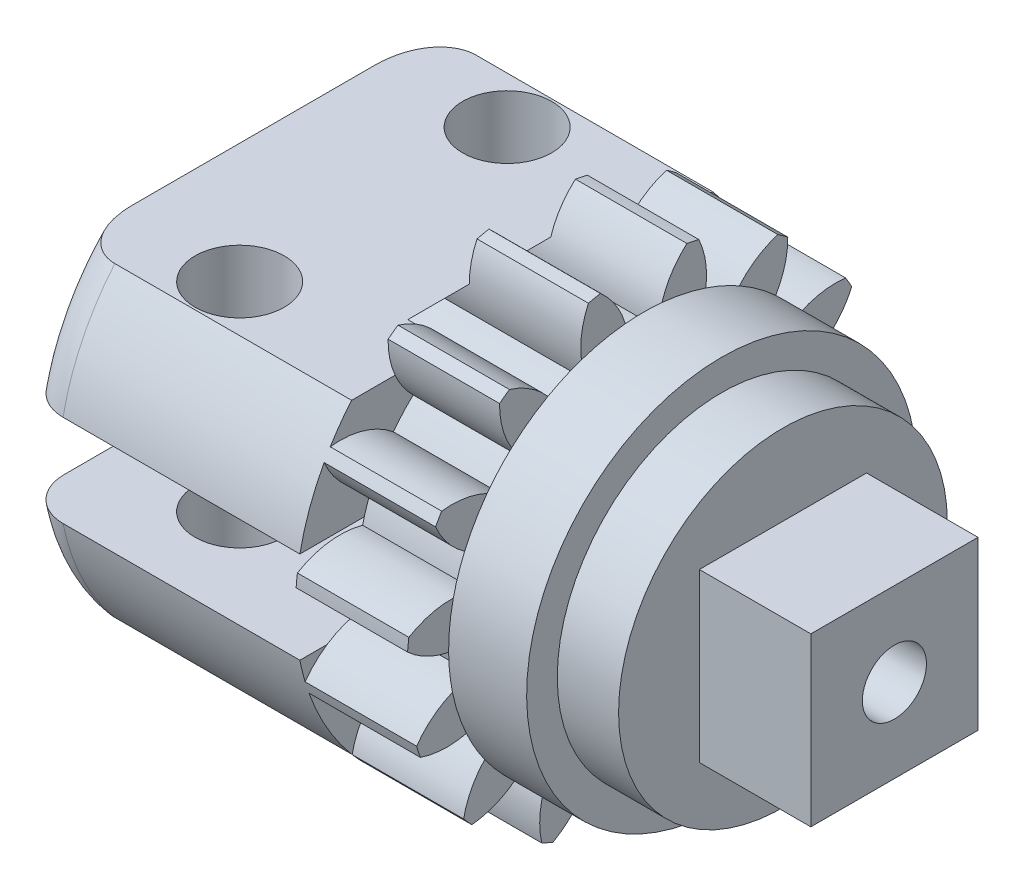
SolidWorks part; units mm, degrees
material "PET"
ref_plane "Plane1" through (0, 0, 0) normal (0, 0, 1) x (1, 0, 0)
ref_plane "Plane2" through (0, 0, 0) normal (0, 1, 0) x (1, 0, 0)
ref_plane "Plane3" through (0, 0, 0) normal (1, 0, 0) x (0, 0, -1)
sketch "HoldingSke" plane through (0, 0, 0) normal (0, 1, 0) x (1, 0, 0)
  line L0 (0, 0) -> (0.9659, -0.2588)
  line L1 (-15, 0) -> (100, 0) construction
  line L2 (0, 0) -> (-2.1039, 2.3779)
  line L3 (0, 0) -> (-11.863, 4.5341)
  line L4 (0, 0) -> (8.3417, 2.2352)
  line L5 (0, 0) -> (-46.8476, -17.4728)
  line L6 (0, 0) -> (-3.3159, -2.2372)
  line L7 (-2.1039, 2.3779) -> (8.6586, 51.2059)
  line L8 (-76.2, 54.61) -> (-76.1, 54.61)
  line L9 (-71.009, 38.7566) -> (-53.1078, 45.2721)
  line L10 (-76.2, 71.12) -> (104.1128, 71.12)
  line L11 (0, 0) -> (-4, 0)
  line L12 (-76.2, 101.6) -> (-76.162, 101.6)
  line L13 (24.9733, 27.94) -> (52.9518, 28.4284)
  line L14 (24.9733, 27.94) -> (24.9743, 27.94)
  line L15 (24.9733, 27.94) -> (100.4006, 29.5858)
  line L16 (-63.627, -1) -> (-12.827, -1)
  circle A0 centre (0, 0) radius 0.4
  circle A1 centre (0, 0) radius 6.249
  circle A2 centre (0, 0) radius 37.5
  circle A3 centre (0, 0) radius 0.4
  dimension "MHD" = 12.498
  dimension "Hub_dia" = 75
  dimension "Bore" = 0.8
  dimension "MBD" = 0.8
  dimension "Num_teeth" = 15
  dimension "Pitch" = 1
  dimension "Overall_len" = 50
  dimension "Show_teeth" = 15
  dimension "Thickness" = 4
  dimension "OAL" = 50.0001
  dimension "T_dim" = 0.1
  dimension "Ap" = 20
  dimension "H" = 19.05
  dimension "Pitch_radius" = 180.3128
  dimension "Width" = 4
  dimension "Backlash" = 0.038
  dimension "Addendum_fac" = 1
  dimension "Dedendum_fac" = 1.25
  dimension "Clearance_fac" = 0.25
  dimension "Dedendum_add" = 0.001
  dimension "Module" = 1
sketch "BasProSke" plane through (0, 0, 0) normal (0, 1, 0) x (1, 0, 0)
  line L0 (-10, 0) -> (60, 0) construction
  line L1 (0, 0) -> (0, 8.5)
  line L2 (0, 0) -> (4, 0)
  line L3 (4, 0) -> (4, 8.5)
  line L4 (4, 8.5) -> (0, 8.5)
  dimension "Thickness" = 4
  dimension "Diameter" = 17
revolve "Base-Revolve" add sketch "BasProSke" angle 360 about L0
sketch "TooCutSke" plane through (0, 0, 0) normal (1, 0, 0) x (0, 0, -1)
  line L1 (0, 0) -> (0, 107) construction
  line L2 (0, 0) -> (-0.8504, 7.4516) construction
  line L3 (0, 0) -> (-3.1044, 14.6049) construction
  line L4 (-0.8504, 7.4516) -> (-1.5522, 7.3025) construction
  arc A0 (0.5316, 6.2263) -> (-0.5316, 6.2263) centre (0, 0) ccw
  arc A1 (1.5766, 8.3784) -> (-1.5766, 8.3784) centre (0, 0) ccw
  circle A2 centre (0, 0) radius 7.5 construction
  circle A3 centre (0, 0) radius 7.0477 construction
  arc A4 (-0.5316, 6.2263) -> (-1.5766, 8.3784) centre (-3.5289, 6.1005) ccw
  arc A5 (1.5766, 8.3784) -> (0.5316, 6.2263) centre (3.5289, 6.1005) ccw
  dimension "Root_dia" = 12.498
  dimension "Overcut_dia" = 17.0508
  dimension "Pitch_dia" = 15
  dimension "Base_dia" = 14.0954
  dimension "Flank_rad" = 3
  dimension "Half_ang" = 12
  dimension "Half_CT" = 0.7175
extrude "ToothCut" cut sketch "TooCutSke" along normal through all
fillet "Breaks" [suppressed] radius 0.02
fillet "RootFillets" [suppressed] radius 0.251
pattern_circular "TeethCuts" count 15 every 24 about axis through (-10, 0, 0) along (1, 0, 0) of "ToothCut", "RootFillets", "Breaks"
sketch "HubNeaOneSke" plane through (0, 0, 0) normal (-1, 0, 0) x (0, 0, 1)
  circle A0 centre (0, 0) radius 6.249
  dimension "Diameter" = 12.498
extrude "HubNearOne" [suppressed] add sketch "HubNeaOneSke" along normal blind 46.0001
sketch "HubNeaBotSke" plane through (0, 0, 0) normal (-1, 0, 0) x (0, 0, 1)
  circle A0 centre (0, 0) radius 6.249
  dimension "Diameter" = 12.498
extrude "HubNearBoth" [suppressed] add sketch "HubNeaBotSke" along normal blind 23
ref_plane "FarPln" through (4, 0, 0) normal (1, 0, 0) x (0, 0, -1)
sketch "HubFarSke" plane through (4, 0, 0) normal (1, 0, 0) x (0, 0, -1)
  circle A0 centre (0, 0) radius 6.249
  dimension "Diameter" = 12.498
extrude "HubFar" [suppressed] add sketch "HubFarSke" along normal blind 23
sketch "BorSke" plane through (0, 0, 0) normal (1, 0, 0) x (0, 0, -1)
  circle A0 centre (0, 0) radius 0.4
  dimension "Diameter" = 0.8
extrude "Bore" cut sketch "BorSke" along normal mid plane 100.0001
sketch "KeySke" plane through (0, 0, 0) normal (1, 0, 0) x (0, 0, -1)
  line L0 (-0.05, 0) -> (-0.05, 0.5)
  line L1 (-0.05, 0.5) -> (0.05, 0.5)
  line L2 (0.05, 0.5) -> (0.05, 0)
  line L3 (0, 0) -> (0, 34) construction
  line L4 (-0.05, 0) -> (0.05, 0)
  dimension "Offset" = 0.5
  dimension "Width" = 0.1
extrude "Keyway" [suppressed] cut sketch "KeySke" along normal mid plane 100.0001
pattern_circular "Keyway2" [suppressed] count 2 every 90 about axis through (-10, 0, 0) along (1, 0, 0)
sketch "Эскиз2" plane through (4, 0, 0) normal (1, 0, 0) x (0, 0, -1)
  circle A0 centre (0, 0) radius 7
  dimension "D1" = 14
extrude "Бобышка-Вытянуть1" add sketch "Эскиз2" along normal blind 2.8
sketch "Эскиз3" plane through (6.8, 0, 0) normal (1, 0, 0) x (0, 0, -1)
  circle A0 centre (0, 0) radius 5.9
  dimension "D1" = 11.8
extrude "Бобышка-Вытянуть2" add sketch "Эскиз3" along normal blind 2.2
sketch "Эскиз4" plane through (9, 0, 0) normal (1, 0, 0) x (0, 0, -1)
  line L1 (-3, 3) -> (3, 3)
  line L2 (-3, 3) -> (-3, -3)
  line L3 (-3, -3) -> (3, -3)
  line L4 (3, 3) -> (3, -3)
  line L5 (-3, 3) -> (3, -3) construction
  line L6 (-3, -3) -> (3, 3) construction
  point P0 (0, 0)
  dimension "D1" = 6
  dimension "D2" = 6
extrude "Бобышка-Вытянуть3" add sketch "Эскиз4" along normal blind 4
sketch "Эскиз5" plane through (0, 0, 0) normal (-1, 0, 0) x (0, 0, 1)
  line L0 (0, 0) -> (-16.1137, 0) construction
  line L1 (9.8464, -5.5) -> (-9.8464, -5.5)
  line L2 (9.8464, -5.5) -> (9.8464, -1.65)
  line L3 (9.8464, -1.65) -> (-9.8464, -1.65)
  line L4 (-9.8464, -5.5) -> (-9.8464, -1.65)
  line L5 (9.8464, -5.5) -> (-9.8464, -1.65) construction
  line L6 (9.8464, -1.65) -> (-9.8464, -5.5) construction
  line L7 (9.8464, 1.65) -> (-9.8464, 1.65)
  line L8 (9.8464, 1.65) -> (9.8464, 5.5)
  line L9 (9.8464, 5.5) -> (-9.8464, 5.5)
  line L10 (-9.8464, 1.65) -> (-9.8464, 5.5)
  line L11 (9.8464, 1.65) -> (-9.8464, 5.5) construction
  line L12 (9.8464, 5.5) -> (-9.8464, 1.65) construction
  point P0 (0, -3.575)
  point P5 (0, 3.575)
  dimension "D1" = 3.3
  dimension "D2" = 11
extrude "Бобышка-Вытянуть4" add sketch "Эскиз5" along normal blind 10
sketch "Эскиз7" plane through (0, 5.5, 0) normal (0, 1, 0) x (1, 0, 0)
  line L0 (-5.7, 10.4662) -> (-5.7, -11.0455) construction
  line L1 (-10, -9.8464) -> (-10, 9.8464) construction
  line L2 (-5.7, -0.2896) -> (-18.3125, -0.2896) construction
  line L3 (0, 0) -> (-22.8613, 0) construction
  line L4 (0, 0.5316) -> (0, -0.5316) construction
  circle A0 centre (-5.7, 4.8) radius 1.6
  circle A1 centre (-5.7, -4.8) radius 1.6
  dimension "D2" = 9.6
  dimension "D3" = 3.2
  dimension "D1" = 4.3
extrude "Вырез-Вытянуть1" cut sketch "Эскиз7" against normal through all
sketch "Эскиз8" plane through (0, 0, 0) normal (-1, 0, 0) x (0, 0, 1)
  circle A0 centre (0, 0) radius 8.5
  circle A1 centre (0, 0) radius 15.2903
  dimension "D1" = 17
extrude "Вырез-Вытянуть2" cut sketch "Эскиз8" along normal through all
sketch "Эскиз9" plane through (0, 0, 0) normal (-1, 0, 0) x (0, 0, 1)
  circle A0 centre (0, 0) radius 1.15
  dimension "D1" = 2.3
extrude "Вырез-Вытянуть3" cut sketch "Эскиз9" against normal through all
chamfer "Фаска1" distance 1.5 angle 45 7 edges at (0, -6.1124, 1.2992) (0, 6.249, 0) (0, -6.1124, -1.2992) (0, 5.7206, -2.5148) (0, -5.5, 0) (0, 5.7206, 2.5148) (0, 5.5, 0)
fillet "Скругление1" radius 1.5 4 edges at (-10, 3.6937, -7.6555) (-10, 3.6937, 7.6555) (-10, -3.6937, 7.6555) (-10, -3.6937, -7.6555)
equation "' \"Module@HoldingSke\" = 6.35"
equation "' \"Num_teeth@HoldingSke\" = 12"
equation "' \"Ap@HoldingSke\" =  20"
equation "' \"Ap@HoldingSke\" = 20"
equation "' \"Width@HoldingSke\" = 0.5 * 25.4"
equation "' \"Hub_dia@HoldingSke\"= 1 * 25.4"
equation "' \"Hub_dia@HoldingSke\" = 1 * 25.4"
equation "' \"Overall_len@HoldingSke\" = 1.0 * 25.4"
equation "' \"Bore@HoldingSke\" = 0.75 * 25.4"
equation "' \"T_dim@HoldingSke\" = 0.1 * 25.4"
equation "' \"Width@KeySke\" = 0.25 * 25.4"
equation "' \"Show_teeth@HoldingSke\" = 13"
equation "' \"Backlash@HoldingSke\" = 0.009 * 25.4"
equation "' \"Addendum_fac@HoldingSke\" = 1.0"
equation "' \"Dedendum_fac@HoldingSke\" = 1.25"
equation "' \"Dedendum_add@HoldingSke\" = 0.00005 * 25.4"
equation "' \"Clearance_fac@HoldingSke\" = 0.25"
equation "\"Pitch@HoldingSke\" = 1 / \"Module@HoldingSke\""
equation "\"Overcut_dia@TooCutSke\" = (\"Num_teeth@HoldingSke\" + 2 * \"Addendum_fac@HoldingSke\") / \"Pitch@HoldingSke\" + 0.002 * 25.4"
equation "\"Pitch_dia@TooCutSke\" = \"Num_teeth@HoldingSke\" / \"Pitch@HoldingSke\""
equation "\"Base_dia@TooCutSke\" = \"Num_teeth@HoldingSke\" / \"Pitch@HoldingSke\" * cos((\"Ap@HoldingSke\"  * 3.14159265 / 180))"
equation "\"Root_dia@TooCutSke\" = (\"Num_teeth@HoldingSke\" + 2) / \"Pitch@HoldingSke\" - 2 * (\"Addendum_fac@HoldingSke\" + \"Dedendum_fac@HoldingSke\") / \"Pitch@HoldingSke\" - \"Dedendum_add@HoldingSke\" * 2"
equation "\"Half_ang@TooCutSke\" = 180 / \"Num_teeth@HoldingSke\""
equation "\"Half_CT@TooCutSke\" = \"Num_teeth@HoldingSke\" / \"Pitch@HoldingSke\" * sin((3.14159265 / 2 / \"Num_teeth@HoldingSke\")) / 2 - 7 * \"Backlash@HoldingSke\" / 4"
equation "\"Flank_rad@TooCutSke\" = \"Num_teeth@HoldingSke\" / \"Pitch@HoldingSke\" / 5"
equation "\"Radius@RootFillets\" = \"Clearance_fac@HoldingSke\" / \"Pitch@HoldingSke\" + \"Dedendum_add@HoldingSke\""
equation "\"Break_rad@Breaks\" = 0.02 / \"Pitch@HoldingSke\""
equation "\"Thickness@HoldingSke\" = \"Width@HoldingSke\""
equation "\"OAL@HoldingSke\" = \"Thickness@HoldingSke\""
equation "\"MHD@HoldingSke\" = (\"Num_teeth@HoldingSke\" + 2) / \"Pitch@HoldingSke\" - 2 * (\"Addendum_fac@HoldingSke\" + \"Dedendum_fac@HoldingSke\")  / \"Pitch@HoldingSke\" - \"Dedendum_add@HoldingSke\" * 2"
equation "\"MBD@HoldingSke\" = (\"Num_teeth@HoldingSke\" + 2) / \"Pitch@HoldingSke\" - 2 * (\"Addendum_fac@HoldingSke\" + \"Dedendum_fac@HoldingSke\")  / \"Pitch@HoldingSke\" - \"Dedendum_add@HoldingSke\" * 2 - 0.002 * 25.4"
equation "\"MHD@HoldingSke\" = ((sgn( \"MHD@HoldingSke\" - \"Hub_dia@HoldingSke\" )-1)*( \"MHD@HoldingSke\" - \"Hub_dia@HoldingSke\" ))/-2+ \"Hub_dia@HoldingSke\""
equation "\"MBD@HoldingSke\" = ((sgn( \"MBD@HoldingSke\" - \"Bore@HoldingSke\" )-1)*( \"MBD@HoldingSke\" - \"Bore@HoldingSke\" ))/-2+ \"Bore@HoldingSke\""
equation "\"OAL@HoldingSke\" = ((sgn( \"OAL@HoldingSke\" - \"Overall_len@HoldingSke\" )+1)*( \"OAL@HoldingSke\" - \"Overall_len@HoldingSke\" ))/2 + \"Overall_len@HoldingSke\" + 0.000002 * 25.4"
equation "\"Num_teeth@TeethCuts\" = int( \"Show_teeth@HoldingSke\" ) + 1"
equation "\"Num_teeth@TeethCuts\" = ((sgn( \"Num_teeth@TeethCuts\" - \"Num_teeth@HoldingSke\" )-1)*( \"Num_teeth@TeethCuts\" - \"Num_teeth@HoldingSke\" ))/-2+ \"Num_teeth@HoldingSke\""
equation "\"Num_teeth@TeethCuts\" = ((sgn( \"Num_teeth@TeethCuts\" - 2.0)+1)*( \"Num_teeth@TeethCuts\" - 2.0))/2 +2.0"
equation "\"Angle@TeethCuts\" = 360.0 / \"Num_teeth@HoldingSke\""
equation "\"Diameter@BasProSke\" = (\"Num_teeth@HoldingSke\" + 2 * \"Addendum_fac@HoldingSke\") / \"Pitch@HoldingSke\""
equation "\"Thickness@BasProSke\"  = \"Thickness@HoldingSke\""
equation "' \"Fillet_rad@BasProSke\" =  \"Thickness@HoldingSke\" * 0.05"
equation "' \"Fillet_rad@BasProSke\" = \"Thickness@HoldingSke\" * 0.05"
equation "\"MHD@HoldingSke\" = ((sgn( \"MHD@HoldingSke\" - \"Root_dia@TooCutSke\" )-1)*( \"MHD@HoldingSke\" - \"Root_dia@TooCutSke\" ))/-2+ \"Root_dia@TooCutSke\""
equation "\"Diameter@HubNeaOneSke\" = \"MHD@HoldingSke\""
equation "\"Length@HubNearOne\" = \"OAL@HoldingSke\" - \"Thickness@BasProSke\""
equation "\"Diameter@HubNeaBotSke\" = \"MHD@HoldingSke\""
equation "\"Length@HubNearBoth\" = ( \"OAL@HoldingSke\" - \"Thickness@BasProSke\" ) / 2.0"
equation "\"Thickness@FarPln\" = \"Thickness@BasProSke\""
equation "\"Diameter@HubFarSke\" = \"MHD@HoldingSke\""
equation "\"Length@HubFar\" = ( \"OAL@HoldingSke\" - \"Thickness@BasProSke\" ) / 2.0"
equation "\"Diameter@BorSke\" = \"MBD@HoldingSke\""
equation "\"D1@Bore\" = \"OAL@HoldingSke\" * 2.0"
equation "\"D1@Keyway\" = \"OAL@HoldingSke\" * 2.0"
equation "\"Offset@KeySke\" = \"T_dim@HoldingSke\" + \"MBD@HoldingSke\" / 2.0"
